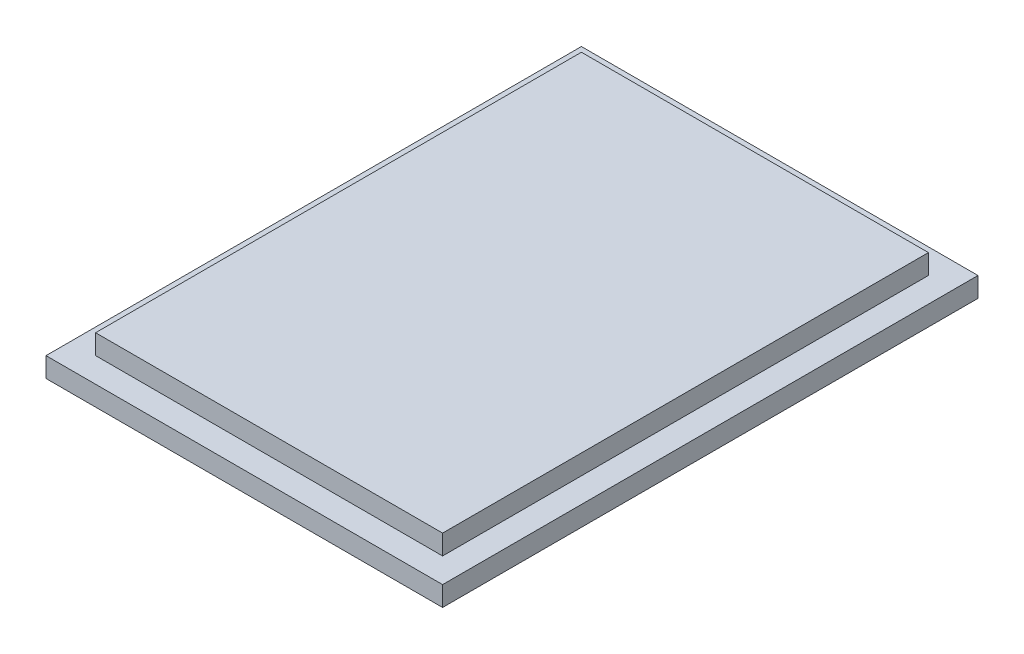
SolidWorks part; units mm, degrees
ref_plane "Alzado" through (0, 0, 0) normal (0, 0, 1) x (1, 0, 0)
ref_plane "Planta" through (0, 0, 0) normal (0, 1, 0) x (1, 0, 0)
ref_plane "Vista lateral" through (0, 0, 0) normal (1, 0, 0) x (0, 0, -1)
sketch "Croquis1" plane through (0, 0, 0) normal (0, 1, 0) x (1, 0, 0)
  line L0 (1.25, 1.25) -> (1.25, 25.75)
  line L1 (0, 0) -> (20, 0)
  line L2 (0, 0) -> (0, 27)
  line L3 (0, 27) -> (20, 27)
  line L4 (20, 0) -> (20, 27)
  line L5 (1.25, 25.75) -> (18.75, 25.75)
  line L6 (18.75, 1.25) -> (18.75, 25.75)
  line L7 (1.25, 1.25) -> (18.75, 1.25)
  dimension "D1" = 27
  dimension "D2" = 20
  dimension "D3" = 1.25
extrude "Saliente-Extruir1" add sketch "Croquis1" along normal blind 1
extrude "Saliente-Extruir2" add sketch "Croquis1<2>" along normal blind 2 contours L0 L7 L6 L5 region at (10, 0, -13.5)
sketch "Croquis1<2>" plane through (0, 0, 0) normal (0, 1, 0) x (1, 0, 0) same geometry as "Croquis1"
